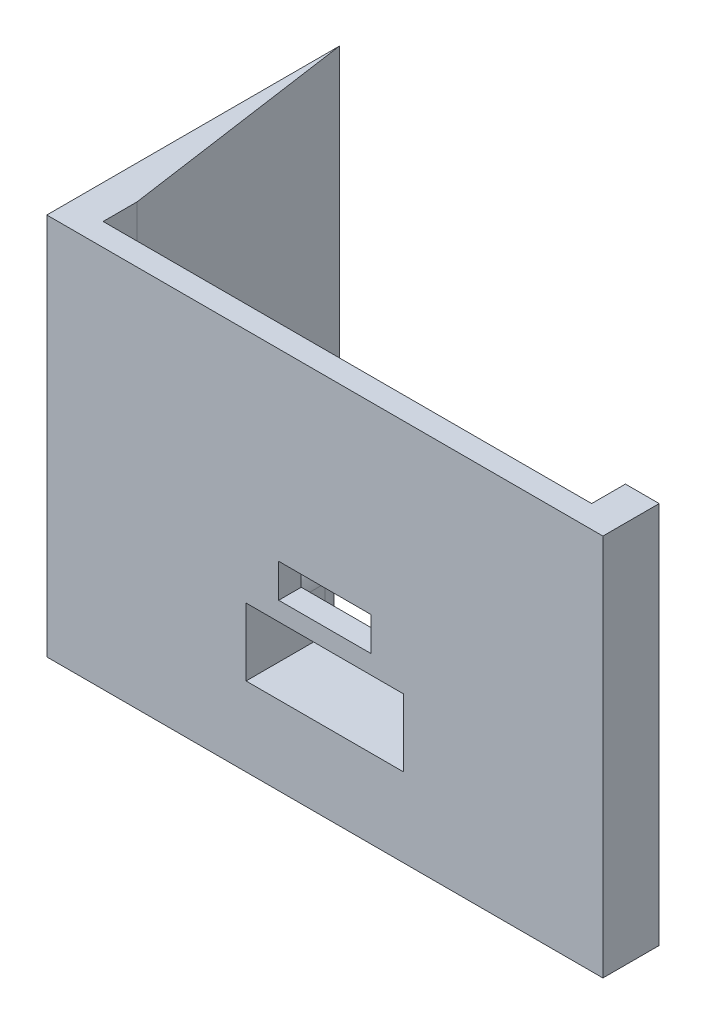
SolidWorks part; units mm, degrees
ref_plane "Front Plane" through (0, 0, 0) normal (0, 0, 1) x (1, 0, 0)
ref_plane "Top Plane" through (0, 0, 0) normal (0, 1, 0) x (1, 0, 0)
ref_plane "Right Plane" through (0, 0, 0) normal (1, 0, 0) x (0, 0, -1)
sketch "Sketch1" plane through (0, 0, 0) normal (0, 1, 0) x (1, 0, 0)
  line L0 (-16.7712, 17.2154) -> (-13.7712, -1.7846)
  line L1 (16.7712, -12.7846) -> (-16.7712, -12.7846)
  line L2 (-13.7712, -4.7846) -> (-13.7712, -1.7846)
  line L4 (-16.7712, -12.7846) -> (-16.7712, 17.2154)
  line L5 (-13.7712, -4.7846) -> (29.6288, -4.7846)
  line L6 (29.6288, -4.7846) -> (29.6288, -1.7846)
  line L7 (29.6288, -1.7846) -> (32.6288, -1.7846)
  line L8 (32.6288, -1.7846) -> (32.6288, -12.7846)
  line L9 (32.6288, -12.7846) -> (16.7712, -12.7846)
  point P0 (0, 0)
extrude "Boss-Extrude3" add sketch "Sketch1" against normal blind 34
sketch "Sketch2" plane through (0, 0, 12.7846) normal (0, 0, 1) x (1, 0, 0)
  line L1 (3.8288, -16.34) -> (3.8288, -10.34)
  line L2 (3.8288, -10.34) -> (12.0288, -10.34)
  line L4 (12.0288, -10.34) -> (12.0288, -16.34)
  line L10 (7.9288, -27) -> (0.9288, -27)
  line L11 (7.9288, -27) -> (14.9288, -27)
  line L12 (14.9288, -27) -> (14.9288, -21)
  line L13 (14.9288, -21) -> (0.9288, -21)
  line L14 (0.9288, -21) -> (0.9288, -27)
  line L15 (7.9288, -19.34) -> (3.8288, -19.34)
  line L16 (7.9288, -19.34) -> (12.0288, -19.34)
  line L17 (12.0288, -19.34) -> (12.0288, -16.34)
  line L19 (3.8288, -16.34) -> (3.8288, -19.34)
extrude "Cut-Extrude1" cut sketch "Sketch2" against normal blind 34
sketch "Sketch3" plane through (0, 0, 12.7846) normal (0, 0, 1) x (1, 0, 0)
  line L0 (3.8288, -10.34) -> (12.0288, -10.34)
  line L1 (12.0288, -16.34) -> (3.8288, -16.34)
  line L2 (12.0288, -19.34) -> (12.0288, -10.34) construction
  line L3 (12.0288, -16.34) -> (12.0288, -10.34)
  line L4 (3.8288, -10.34) -> (3.8288, -19.34) construction
  line L5 (3.8288, -16.34) -> (3.8288, -10.34)
extrude "Boss-Extrude4" add sketch "Sketch3" against normal blind 8
sketch "Sketch4" plane through (0, 0, 4.7846) normal (0, 0, -1) x (-1, 0, 0)
  line L0 (-14.9288, -27) -> (-16.9288, -27)
  line L1 (-16.9288, -27) -> (-16.9288, -28.3308)
  line L2 (-0.9288, -27) -> (1.0712, -27)
  line L3 (1.0712, -27) -> (1.0712, -28.3308)
  line L4 (1.0712, -28.3308) -> (-16.9288, -28.3308)
  line L5 (-14.9288, -27) -> (-0.9288, -27)
extrude "Boss-Extrude5" add sketch "Sketch4" along normal blind 5
sketch "Sketch5" plane through (0, 0, 4.7846) normal (0, 0, -1) x (-1, 0, 0)
  line L0 (-3.8288, -16.34) -> (1.0712, -16.34)
  line L1 (-12.0288, -16.34) -> (-16.9288, -16.34)
  line L2 (1.0712, -16.34) -> (1.0712, -14.34)
  line L3 (1.0712, -14.34) -> (-16.9288, -14.34)
  line L4 (-16.9288, -14.34) -> (-16.9288, -16.34)
  line L5 (-12.0288, -16.34) -> (-3.8288, -16.34)
extrude "Boss-Extrude6" add sketch "Sketch5" along normal blind 5
sketch "Sketch6" plane through (0, 0, 4.7846) normal (0, 0, -1) x (-1, 0, 0)
  line L0 (-12.0288, -16.34) -> (-12.0288, -19.34)
  line L1 (-12.0288, -16.34) -> (-12.0288, -19.34) construction
  line L2 (-12.0288, -19.34) -> (-3.8288, -19.34) construction
  line L3 (-12.0288, -19.34) -> (-14.0288, -19.34)
  line L4 (-14.0288, -19.34) -> (-14.0288, -16.34)
  line L5 (-16.9288, -16.34) -> (1.0712, -16.34) construction
  line L6 (-14.0288, -16.34) -> (-12.0288, -16.34)
  line L7 (-3.8288, -16.34) -> (-1.8288, -16.34)
  line L8 (-1.8288, -16.34) -> (-1.8288, -19.34)
  line L9 (-1.8288, -19.34) -> (-3.8288, -19.34)
  line L10 (-3.8288, -19.34) -> (-3.8288, -16.34)
extrude "Boss-Extrude7" add sketch "Sketch6" along normal blind 5
fillet "Fillet1" radius 1 9 edges at (7.9288, -16.34, -0.2154) (3.8288, -19.34, 2.2846) (12.0288, -19.34, 2.2846) (1.8288, -17.84, -0.2154) (2.8288, -19.34, -0.2154) (14.0288, -17.84, -0.2154) (13.0288, -19.34, -0.2154) (3.8288, -17.84, -0.2154) (12.0288, -17.84, -0.2154)
sketch "Sketch7" plane through (0, 0, 4.7846) normal (0, 0, -1) x (-1, 0, 0)
  line L0 (-14.9288, -27) -> (-14.9288, -21)
  line L1 (-14.9288, -21) -> (-16.9288, -21)
  line L2 (-16.9288, -21) -> (-16.9288, -27)
  line L3 (-16.9288, -27) -> (-14.9288, -27)
  line L4 (-0.9288, -21) -> (1.0712, -21)
  line L5 (-0.9288, -21) -> (-14.9288, -21) construction
  line L6 (-0.9288, -27) -> (-0.9288, -21) construction
  line L7 (1.0712, -21) -> (1.0712, -27)
  line L8 (1.0712, -27) -> (-0.9288, -27)
  line L9 (-0.9288, -27) -> (-0.9288, -21)
extrude "Boss-Extrude8" add sketch "Sketch7" along normal blind 5
fillet "Fillet2" radius 1 7 edges at (0.9288, -24, -0.2154) (-0.0712, -21, -0.2154) (0.9288, -21, 2.2846) (7.9288, -27, -0.2154) (14.9288, -24, -0.2154) (15.9288, -21, -0.2154) (14.9288, -21, 2.2846)
sketch "Sketch8" plane through (0, 0, -0.2154) normal (0, 0, -1) x (-1, 0, 0)
  line L0 (-14.0288, -16.34) -> (-14.0288, -14.34)
  line L1 (1.0712, -14.34) -> (-16.9288, -14.34) construction
  line L2 (-14.0288, -14.34) -> (-16.9288, -14.34)
  line L3 (-16.9288, -14.34) -> (-16.9288, -16.34)
  line L4 (-16.9288, -16.34) -> (-14.0288, -16.34)
  line L5 (-1.8288, -16.34) -> (-1.8288, -14.34)
  line L6 (1.0712, -14.34) -> (-16.9288, -14.34) construction
  line L7 (-1.8288, -14.34) -> (1.0712, -14.34)
  line L8 (1.0712, -14.34) -> (1.0712, -16.34)
  line L9 (1.0712, -16.34) -> (-1.8288, -16.34)
extrude "Cut-Extrude2" cut sketch "Sketch8" against normal blind 5
sketch "Sketch9" plane through (0, 0, 4.7846) normal (0, 0, -1) x (-1, 0, 0)
  line L0 (-29.6288, 0) -> (13.7712, 0)
  line L1 (13.7712, 0) -> (13.7712, -34)
  line L2 (13.7712, -34) -> (-29.6288, -34)
  line L3 (-29.6288, -34) -> (-29.6288, 0)
extrude "Cut-Extrude4" cut sketch "Sketch9" against normal blind 2
sketch "Sketch12" plane through (0, 0, -0.2154) normal (0, 0, -1) x (-1, 0, 0)
  line L0 (-14.0288, -14.34) -> (-1.8288, -14.34)
  line L1 (-1.8288, -14.34) -> (-1.8288, -19.34)
  line L2 (-2.8288, -18.34) -> (-1.8288, -19.34) construction
  line L3 (-1.8288, -19.34) -> (-3.8288, -19.34)
  line L4 (-3.8288, -19.34) -> (-3.8288, -16.34)
  line L5 (-3.8288, -16.34) -> (-12.0288, -16.34)
  line L6 (-3.8288, -16.34) -> (-12.0288, -16.34) construction
  line L7 (-12.0288, -16.34) -> (-12.0288, -18.34) construction
  line L8 (-12.0288, -16.34) -> (-12.0288, -19.34)
  line L9 (-12.0288, -19.34) -> (-14.0288, -19.34)
  line L10 (-14.0288, -19.34) -> (-13.0288, -18.34) construction
  line L11 (-14.0288, -19.34) -> (-14.0288, -14.34)
  line L12 (-16.9383, -20.9841) -> (-14.9288, -21)
  line L13 (-14.9288, -21) -> (-14.9288, -27)
  line L14 (-14.9288, -27) -> (-0.9288, -27)
  line L15 (-0.9288, -27) -> (-0.9288, -21)
  line L16 (-0.9288, -21) -> (-14.9288, -21) construction
  line L17 (-0.9288, -21) -> (1.0712, -21)
  line L18 (1.0712, -21) -> (1.0712, -28.3308)
  line L19 (-16.9288, -28.3308) -> (1.0712, -28.3308) construction
  line L20 (1.0712, -28.3308) -> (-16.9288, -28.3308)
  line L21 (-16.9288, -28.3308) -> (-16.9383, -20.9841)
  line L22 (-16.9288, -22) -> (-16.9288, -28.3308) construction
extrude "Boss-Extrude9" add sketch "Sketch12" against normal blind 7
fillet "Fillet5" radius 2 5 edges at (3.8288, -19.34, 3.2846) (3.8288, -17.84, -0.2154) (7.9288, -16.34, -0.2154) (12.0288, -19.34, 3.2846) (12.0288, -17.84, -0.2154)
fillet "Fillet6" radius 2 6 edges at (0.9288, -24, -0.2154) (0.9288, -21, 3.2846) (7.9288, -27, -0.2154) (14.9288, -24, -0.2154) (15.9335, -20.992, -0.2154) (14.9288, -21, 3.2846)
sketch "Sketch13" plane through (0, 0, 0) normal (0, 1, 0) x (1, 0, 0)
  line L0 (-16.7712, -12.7846) -> (-16.7712, -8.7846)
  line L1 (-16.7712, 17.2154) -> (-16.7712, -12.7846) construction
  line L2 (-16.7712, -8.7846) -> (32.6288, -8.7846)
  line L3 (32.6288, -12.7846) -> (32.6288, -1.7846) construction
  line L4 (32.6288, -8.7846) -> (32.6288, -12.7846)
  line L5 (32.6288, -12.7846) -> (-16.7712, -12.7846)
  line L6 (-16.7712, -12.7846) -> (-16.6704, -12.921)
  line M5 (-16.7712, 17.2154) -> (-16.7712, -12.7846)
  line M6 (-16.7712, -12.7846) -> (32.6288, -12.7846)
  line M7 (32.6288, -12.7846) -> (32.6288, -1.7846)
extrude "Cut-Extrude5" cut sketch "Sketch13" against normal blind 40 contours L2 M5 M6 M7 region at (7.9288, 0, 10.7846)
sketch "Sketch15" plane through (0, 0, 0) normal (0, 1, 0) x (1, 0, 0)
  line L0 (29.6288, -1.7846) -> (32.6288, -1.7846)
  line L1 (32.6288, -1.7846) -> (32.6288, -4.7846)
  line L2 (32.6288, -8.7846) -> (32.6288, -1.7846) construction
  line L3 (32.6288, -4.7846) -> (29.6288, -4.7846)
  line L4 (29.6288, -1.7846) -> (29.6288, -6.7846) construction
  line L5 (29.6288, -4.7846) -> (29.6288, -1.7846)
extrude "Cut-Extrude6" cut sketch "Sketch15" against normal blind 50
sketch "Sketch16" plane through (0, 0, 0) normal (0, 1, 0) x (1, 0, 0)
  line L1 (-13.7712, -6.7846) -> (-13.7712, -1.7846) construction
  line L2 (-13.7712, -3.7846) -> (-16.7712, 17.2154)
  line L3 (-16.7712, 17.2154) -> (-13.7712, 17.2154)
  line L4 (-13.7712, 17.2154) -> (-13.7712, -3.7846)
extrude "Cut-Extrude7" cut sketch "Sketch16" against normal blind 50
sketch "Sketch17" plane through (0, 0, 4.7846) normal (0, 0, -1) x (-1, 0, 0)
  line L0 (-32.6288, 0) -> (-29.6288, 0)
  line L1 (-29.6288, 0) -> (-29.6288, -34)
  line L2 (-32.6288, 0) -> (-32.6288, -34)
  line L3 (-32.6288, -34) -> (-29.6288, -34)
extrude "Boss-Extrude10" add sketch "Sketch17" along normal blind 1
